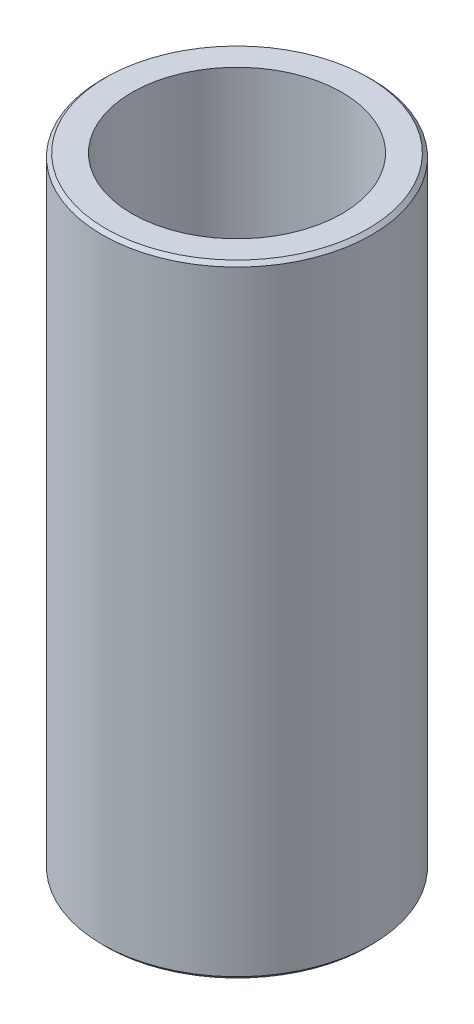
SolidWorks part; units mm, degrees
ref_plane "Front Plane" through (0, 0, 0) normal (0, 0, 1) x (1, 0, 0)
ref_plane "Top Plane" through (0, 0, 0) normal (0, 1, 0) x (1, 0, 0)
ref_plane "Right Plane" through (0, 0, 0) normal (1, 0, 0) x (0, 0, -1)
sketch "Sketch1" plane through (0, 0, 0) normal (0, 1, 0) x (1, 0, 0)
  circle A0 centre (0, 0) radius 30
  dimension "SHAFT_OD" = 60
extrude "Boss-Extrude1" add sketch "Sketch1" along normal blind 138.4113
sketch "Sketch2" plane through (0, 0, 0) normal (0, 1, 0) x (1, 0, 0)
  circle A0 centre (0, 0) radius 23.3902
  dimension "BORE_D" = 46.7804
extrude "Cut-Extrude1" cut sketch "Sketch2" along normal through all
chamfer "Chamfer1" distance 0.7825 angle 46.065 2 edges at (0, 138.4113, 30) (0, 0, 30) first distance on face at (0, 138.4113, 30) first distance on face at (0, 0, 23.3902)
